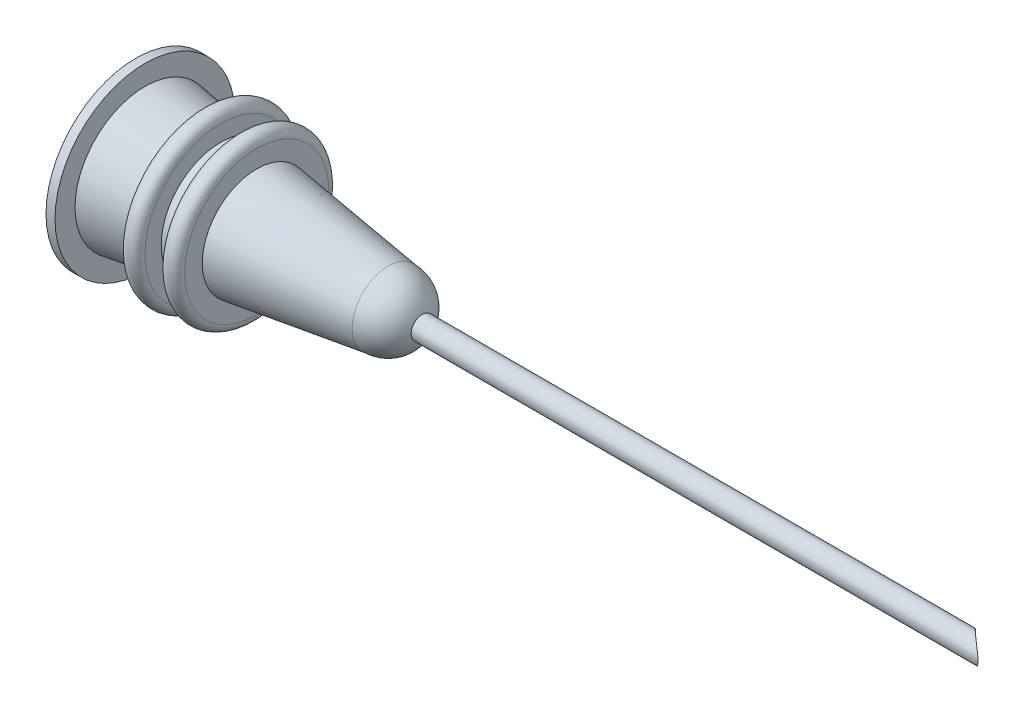
SolidWorks part; units mm, degrees
ref_plane "Front Plane" through (0, 0, 0) normal (0, 0, 1) x (1, 0, 0)
ref_plane "Top Plane" through (0, 0, 0) normal (0, 1, 0) x (1, 0, 0)
ref_plane "Right Plane" through (0, 0, 0) normal (1, 0, 0) x (0, 0, -1)
sketch "Sketch2" plane through (0, 0, 0) normal (0, 0, 1) x (1, 0, 0)
  line L0 (-26.1797, 0) -> (0, 0) construction
  line L1 (0, 0) -> (-1, 0)
  line L2 (0, 0) -> (0, 2)
  line L3 (0, 2) -> (-7.3, 3.0219)
  line L4 (-13.5, 3.8899) -> (-13.5, 5)
  line L5 (-14, 3.2402) -> (-14, 5)
  line L6 (-1, 0) -> (-1, 1.3827)
  line L7 (-14, 3.2025) -> (-1, 1.3827)
  line L8 (-14, 5) -> (-13.5, 5)
  line L9 (-10.3, 4.2) -> (-10.3, 3.4419)
  line L10 (-9.3, 4.2) -> (-9.3, 3.3019)
  line L11 (-8.3, 4) -> (-8.3, 3.1619)
  line L12 (-7.3, 4) -> (-7.3, 3.0219)
  line L13 (-10.3, 3.4419) -> (-13.5, 3.8899)
  line L14 (-8.3, 3.1619) -> (-9.3, 3.3019)
  line L15 (-14, 3.2025) -> (-14, 3.2402)
  arc A0 (-9.3, 4.2) -> (-10.3, 4.2) centre (-9.8, 4.2) ccw
  arc A1 (-7.3, 4) -> (-8.3, 4) centre (-7.8, 4) ccw
  dimension "D7" = 1
  dimension "D8" = 1
  dimension "D1" = 1
  dimension "D2" = 2
  dimension "D3" = 0.75
  dimension "D4" = 14
  dimension "D5" = 0.5
  dimension "D6" = 5
  dimension "D9" = 4
  dimension "D10" = 4.2
  dimension "D11" = 2
  dimension "D12" = 7.8
revolve "Revolve1" add sketch "Sketch2" angle 360 about L0
dome "Dome1" faces to dome 1 distance 2 reverse direction no elliptical dome no face at (0, 0, 2) parameters "D1"=2
sketch "Sketch5" plane through (-1, 0, 0) normal (-1, 0, 0) x (0, 0, 1)
  circle A0 centre (0, 0) radius 0.5
  dimension "D1" = 1
extrude "Cut-Extrude1" cut sketch "Sketch5" against normal through all
sketch "Sketch6" plane through (-1, 0, 0) normal (-1, 0, 0) x (0, 0, 1)
  circle A0 centre (0, 0) radius 0.5 construction
  circle A1 centre (0, 0) radius 0.5
extrude "Extrude-Thin1" add sketch "Sketch6" against normal blind 40 thin thin type one direction wall 0.125
sketch "Sketch7" plane through (0, 0, 0) normal (0, 1, 0) x (1, 0, 0)
  line L0 (39, -0.625) -> (39, 7.0426) construction
  circle A0 centre (39, 7.0426) radius 9.5066
extrude "Cut-Extrude2" cut sketch "Sketch7" against normal through all both and the other way through all
